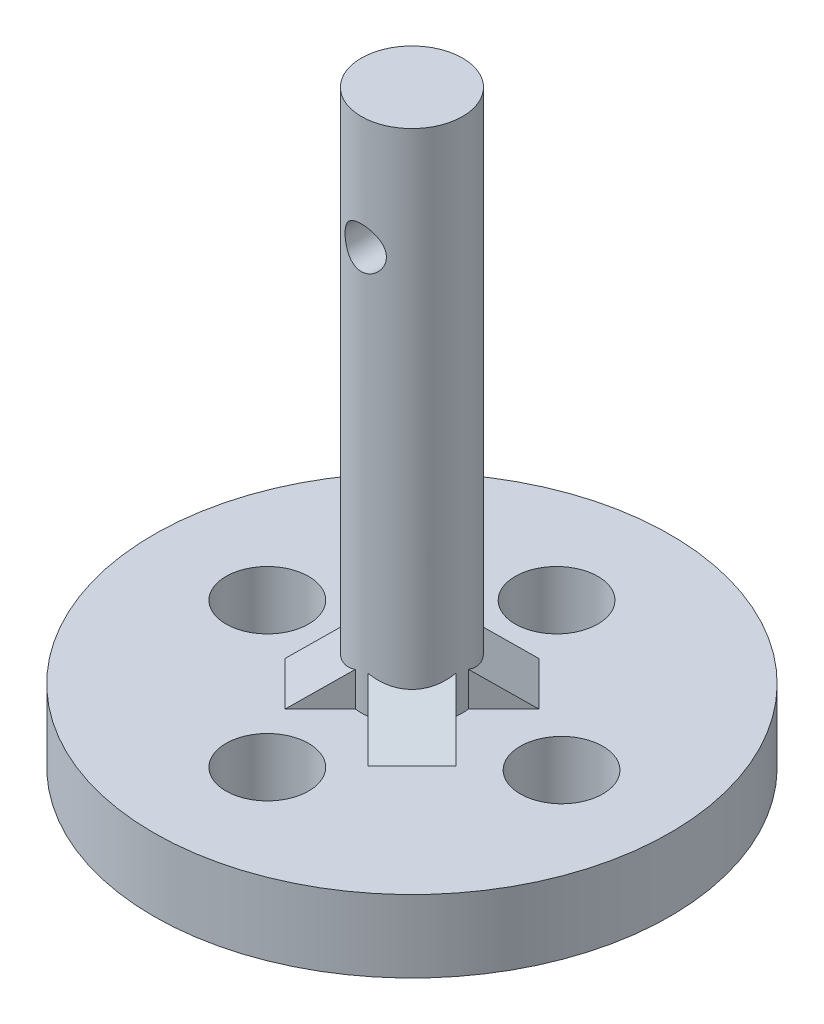
SolidWorks part; units mm, degrees
ref_plane "前视基准面" through (0, 0, 0) normal (0, 0, 1) x (1, 0, 0)
ref_plane "上视基准面" through (0, 0, 0) normal (0, 1, 0) x (1, 0, 0)
ref_plane "右视基准面" through (0, 0, 0) normal (1, 0, 0) x (0, 0, -1)
sketch "草图1" plane through (0, 0, 0) normal (0, 1, 0) x (1, 0, 0)
  circle A0 centre (0, 0) radius 12.5
  dimension "D1" = 25
extrude "凸台-拉伸1" add sketch "草图1" along normal blind 3.5
sketch "草图2" plane through (0, 3.5, 0) normal (0, 1, 0) x (1, 0, 0)
  circle A0 centre (0, 0) radius 2.45
  dimension "D1" = 4.9
extrude "凸台-拉伸2" add sketch "草图2" along normal blind 25
sketch "草图4" plane through (0, 3.5, 0) normal (0, 1, 0) x (1, 0, 0)
  line L0 (0, 0) -> (7.2415, 0)
  line L1 (0, 0) -> (0, 7)
  line L2 (0, 0) -> (-7, 0)
  line L3 (0, 0) -> (0, -7)
  circle A0 centre (0, 7) radius 2
  circle A1 centre (7.2415, 0) radius 2
  circle A2 centre (0, -7) radius 2
  circle A3 centre (-7, 0) radius 2
extrude "切除-拉伸1" cut sketch "草图4" against normal through all contours A0
extrude "切除-拉伸2" cut sketch "草图4<5>" against normal through all contours A3 | A1 | A2 region at (7.2415, 3.5, -1.9434) region at (-8.9434, 3.5, 0) region at (1.3742, 3.5, 5.6258)
sketch "草图4<5>" plane through (0, 3.5, 0) normal (0, 1, 0) x (1, 0, 0) same geometry as "草图4"
sketch3d "3D草图7"
  line L0 (0, 28.5, 0) -> (0, 3.5, 0) construction
  circle A0 centre (0, 23, 0) radius 1
  point P2 (0, 23, 1)
ref_plane "基准面1" through (0, 0, 0) normal (0.7071, 0, 0.7071) x (0, -1, 0)
ref_plane "基准面2" through (0, 0, 0) normal (-0.7071, 0, 0.7071) x (0, -1, 0)
sketch "草图7" plane through (0, 0, 0) normal (1, 0, 0) x (0, 0, -1)
  line L0 (0, 0) -> (0, 6.5)
sketch "草图8" plane through (0, 0, 0) normal (-0.7071, 0, 0.7071) x (0, -1, 0)
  line L0 (-6.5, 0) -> (-3.4094, 5.0197)
rib "筋1" sketch "草图8" sketch "草图8" thickness 3 extrusion direction parallel to sketch draft on no parameters "D1"=3
sketch "草图9" plane through (0, 0, 0) normal (-0.7071, 0, 0.7071) x (0, -1, 0)
  line L0 (-6.5, 0) -> (-3.443, -5.1628)
rib "筋6" sketch "草图9" sketch "草图9" thickness 3 extrusion direction parallel to sketch draft on no parameters "D1"=3
sketch "草图11" plane through (0, 0, 0) normal (0.7071, 0, 0.7071) x (0, -1, 0)
  line L0 (-6.5, 0) -> (-3.0487, 4.9933)
rib "筋7" sketch "草图11" sketch "草图11" thickness 3 extrusion direction parallel to sketch draft on no parameters "D1"=3
mirror "镜向1" about plane through (0, 0, 0) normal (-0.7071, 0, 0.7071) of "筋7"
sketch "草图12" plane through (0, 3.5, 0) normal (0, 1, 0) x (1, 0, 0)
  line L0 (0, 7.6573) -> (0, 0.5299)
extrude "切除-拉伸4" cut sketch "3D草图7" along direction (0, 0, 1) on the side against the normal through all both and the other way through all
